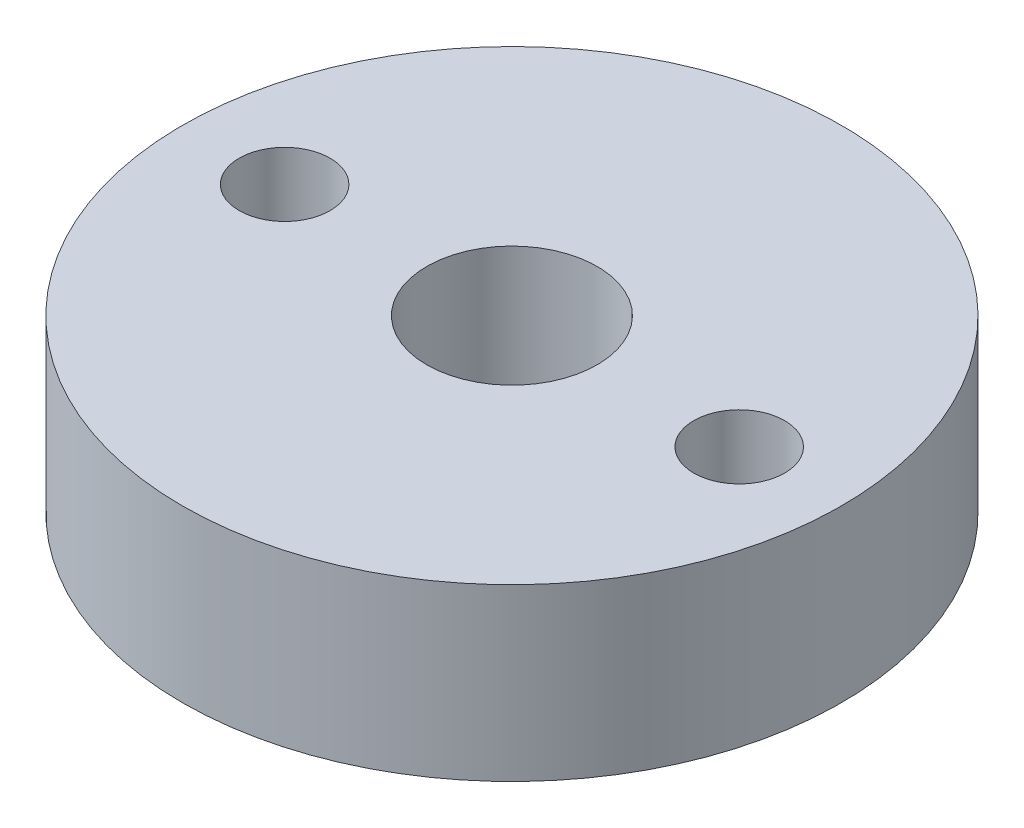
SolidWorks part; units mm, degrees
ref_plane "Plano frontal" through (0, 0, 0) normal (0, 0, 1) x (1, 0, 0)
ref_plane "Plano superior" through (0, 0, 0) normal (0, 1, 0) x (1, 0, 0)
ref_plane "Plano direito" through (0, 0, 0) normal (1, 0, 0) x (0, 0, -1)
ref_plane "Plano1" through (0, -6, 0) normal (0, -1, 0) x (1, 0, 0)
sketch "Esboço1" plane through (0, -6, 0) normal (0, -1, 0) x (1, 0, 0)
  line L0 (-8, 0) -> (8, 0) construction
  circle A0 centre (8, 0) radius 1.6
  circle A1 centre (0, 0) radius 3
  circle A2 centre (-8, 0) radius 1.6
  circle A3 centre (0, 0) radius 11.6
  point P7 (0, 0)
  dimension "D1" = 23.2
  dimension "D2" = 3.2
  dimension "D3" = 6
  dimension "D4" = 16
extrude "Ressalto-extrusão1" add sketch "Esboço1" against normal blind 6
